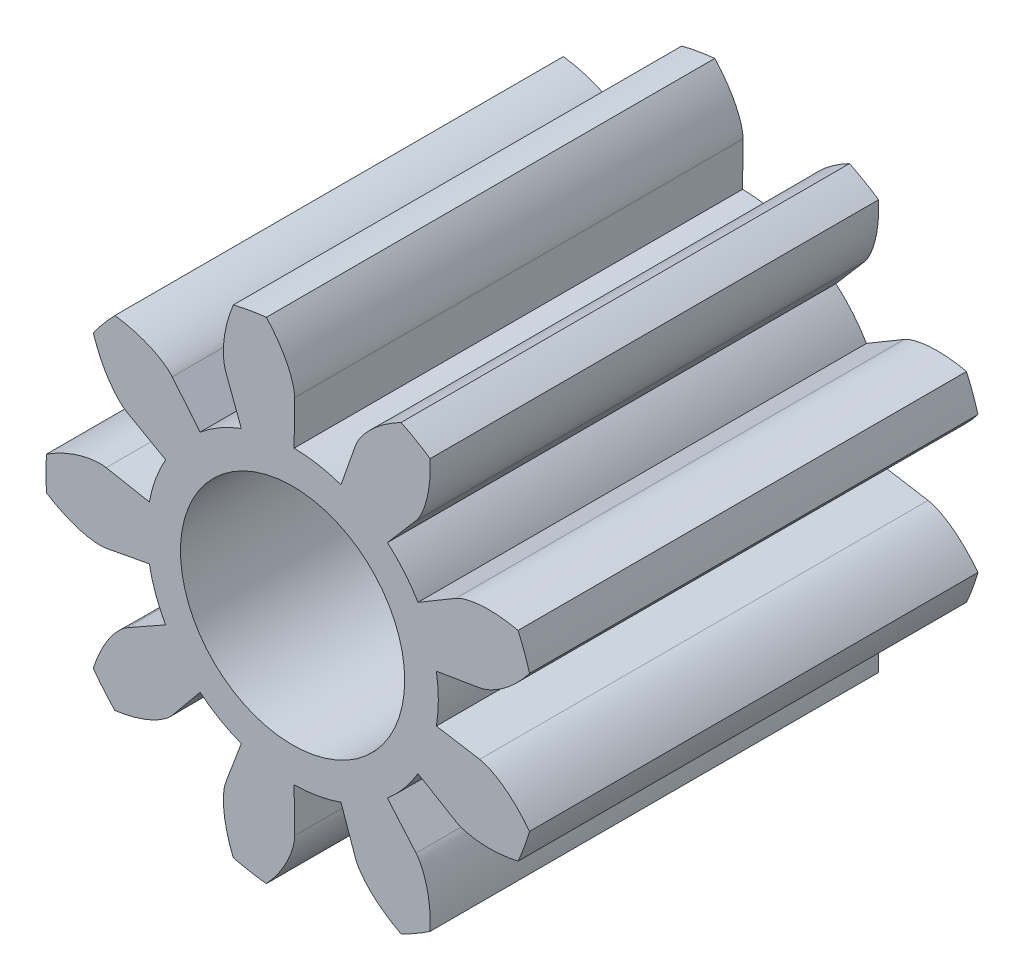
SolidWorks part; units mm, degrees
ref_plane "前视基准面" through (0, 0, 0) normal (0, 0, 1) x (1, 0, 0)
ref_plane "上视基准面" through (0, 0, 0) normal (0, 1, 0) x (1, 0, 0)
ref_plane "右视基准面" through (0, 0, 0) normal (1, 0, 0) x (0, 0, -1)
other "Configuration Table"
sketch "草图1" plane through (0, 0, 0) normal (0, 0, 1) x (1, 0, 0)
  line L0 (0, 0) -> (1.8, 0) construction
  line L1 (0, 0) -> (1.7727, 0.3126) construction
  line L2 (0, 0) -> (1.6688, 0.276)
  line L3 (1.7727, 0.3126) -> (1.7727, -0.3126) construction
  line L4 (0, 0) -> (1.6688, -0.276)
  circle A0 centre (0, 0) radius 2.2
  circle A1 centre (0, 0) radius 1.8 construction
  circle A2 centre (0, 0) radius 1.3
  circle A3 centre (0, 0) radius 1.6914 construction
  circle A4 centre (0, 0) radius 1
  spline S0 degree 4 poles (1.6688, 0.276) (1.6815, 0.2781) (1.7165, 0.2867) (1.7804, 0.3134) (1.8769, 0.3705) (1.9892, 0.4631) (2.115, 0.6012) (2.2366, 0.7836) (2.3401, 1.0009) (2.4181, 1.2482) (2.465, 1.503) (2.4828, 1.7615) (2.473, 2.0332) (2.4258, 2.3665) (2.3192, 2.7541) (2.1304, 3.1816) (1.8506, 3.6185) (1.5097, 4.0103) (1.1213, 4.3527) (0.6893, 4.6421) (0.2307, 4.8777) (-0.2607, 5.0574) (-0.7542, 5.1833) (-1.2841, 5.2523) (-1.6863, 5.2693) (-2.1385, 5.2469) (-2.3948, 5.2166) (-2.6865, 5.1734) (-2.8298, 5.138) (-2.9571, 5.1118) (-2.9949, 5.1006) (-3.0222, 5.094) (-3.037, 5.0905) knots 0 0 0 0 0 0.005604 0.015718 0.02996 0.048734 0.068727 0.096889 0.125051 0.153212 0.181374 0.209535 0.237696 0.271429 0.327752 0.384075 0.440398 0.496721 0.553044 0.609367 0.66569 0.722013 0.778336 0.834659 0.890982 0.909091 0.954545 0.977273 0.988636 0.994318 1 1 1 1 1 construction
  spline S1 degree 4 poles (1.6688, 0.276) (1.6815, 0.2781) (1.7165, 0.2867) (1.7804, 0.3134) (1.8769, 0.3705) (1.9892, 0.4631) (2.115, 0.6012) (2.2366, 0.7836) (2.3401, 1.0009) (2.4181, 1.2482) (2.465, 1.503) (2.4828, 1.7615) (2.473, 2.0332) (2.4258, 2.3665) (2.3192, 2.7541) (2.1304, 3.1816) (1.8506, 3.6185) (1.5097, 4.0103) (1.1213, 4.3527) (0.6893, 4.6421) (0.2307, 4.8777) (-0.2607, 5.0574) (-0.7542, 5.1833) (-1.2841, 5.2523) (-1.6863, 5.2693) (-2.0219, 5.2526) (-2.1774, 5.2392) (-2.215, 5.2356) knots 0 0 0 0 0 0.005604 0.015718 0.02996 0.048734 0.068727 0.096889 0.125051 0.153212 0.181374 0.209535 0.237696 0.271429 0.327752 0.384075 0.440398 0.496721 0.553044 0.609367 0.66569 0.722013 0.778336 0.834659 0.890982 0.909091 0.909091 0.909091 0.909091 0.909091
  spline S2 degree 4 poles (1.6688, -0.276) (1.6815, -0.2781) (1.7165, -0.2867) (1.7804, -0.3134) (1.8769, -0.3705) (1.9892, -0.4631) (2.115, -0.6012) (2.2366, -0.7836) (2.3401, -1.0009) (2.4181, -1.2482) (2.465, -1.503) (2.4828, -1.7615) (2.473, -2.0332) (2.4258, -2.3665) (2.3192, -2.7541) (2.1304, -3.1816) (1.8506, -3.6185) (1.5097, -4.0103) (1.1213, -4.3527) (0.6893, -4.6421) (0.2307, -4.8777) (-0.2607, -5.0574) (-0.7542, -5.1833) (-1.2841, -5.2523) (-1.6863, -5.2693) (-2.1385, -5.2469) (-2.3948, -5.2166) (-2.6865, -5.1734) (-2.8298, -5.138) (-2.9571, -5.1118) (-2.9949, -5.1006) (-3.0222, -5.094) (-3.037, -5.0905) knots 0 0 0 0 0 0.005604 0.015718 0.02996 0.048734 0.068727 0.096889 0.125051 0.153212 0.181374 0.209535 0.237696 0.271429 0.327752 0.384075 0.440398 0.496721 0.553044 0.609367 0.66569 0.722013 0.778336 0.834659 0.890982 0.909091 0.954545 0.977273 0.988636 0.994318 1 1 1 1 1 construction
  spline S3 degree 4 poles (1.6688, -0.276) (1.6815, -0.2781) (1.7165, -0.2867) (1.7804, -0.3134) (1.8769, -0.3705) (1.9892, -0.4631) (2.115, -0.6012) (2.2366, -0.7836) (2.3401, -1.0009) (2.4181, -1.2482) (2.465, -1.503) (2.4828, -1.7615) (2.473, -2.0332) (2.4258, -2.3665) (2.3192, -2.7541) (2.1304, -3.1816) (1.8506, -3.6185) (1.5097, -4.0103) (1.1213, -4.3527) (0.6893, -4.6421) (0.2307, -4.8777) (-0.2607, -5.0574) (-0.7542, -5.1833) (-1.2841, -5.2523) (-1.6863, -5.2693) (-2.0219, -5.2526) (-2.1774, -5.2392) (-2.215, -5.2356) knots 0 0 0 0 0 0.005604 0.015718 0.02996 0.048734 0.068727 0.096889 0.125051 0.153212 0.181374 0.209535 0.237696 0.271429 0.327752 0.384075 0.440398 0.496721 0.553044 0.609367 0.66569 0.722013 0.778336 0.834659 0.890982 0.909091 0.909091 0.909091 0.909091 0.909091
  point P15 (1.7727, 0)
  dimension "齿顶圆直径" = 4.4
  dimension "分度圆直径" = 3.6
  dimension "齿根圆直径" = 2.6
  dimension "基圆直径" = 3.3829
  dimension "内孔直径" = 2
  dimension "渐近线镜像线夹角" = 10
extrude "凸台-拉伸1" add sketch "草图1" along normal blind 4 contours A0 | A4
extrude "切除-拉伸1" cut sketch "草图1<3>" along normal through all contours A2 S3 A0 S1 region at (1.8185, 0, 0)
sketch "草图1<3>" plane through (0, 0, 0) normal (0, 0, 1) x (1, 0, 0) same geometry as "草图1"
pattern_circular "阵列(圆周)1" count 9 every 40 about axis through (0, 0, 4) along (0, 0, 1) of "切除-拉伸1"
equation "\"m\" = 0.4'模数"
equation "\"z\" = 9'齿数"
equation "\"a\"= 20度'压力角"
equation "\"d\"= \"m\" * \"z\"'分度圆直径"
equation "\"da\"= ( \"z\" + 2 ) * \"m\"'齿顶圆直径"
equation "\"df\"= ( \"z\" - 2.5 ) * \"m\"'齿根圆直径"
equation "\"s\"= 0.5 * PI * \"m\"'分度圆齿厚"
equation "\"r\"= 0.38 * \"m\"'齿根圆角"
equation "\"B\"= 0.3 * \"d\"'齿厚"
equation "\"db\"= \"m\" * \"z\" * cos ( \"a\" )'基圆直径"
equation "\"rb\"= \"db\" / 2'基圆半径"
equation "\"齿顶圆直径@草图1\"= \"da\""
equation "\"分度圆直径@草图1\"= \"d\""
equation "\"齿根圆直径@草图1\"= \"df\""
equation "\"基圆直径@草图1\"= \"db\""
equation "\"渐近线镜像线夹角@草图1\"= 360 / 4 / \"z\""
equation "\"h\"= 4'齿轮厚度"
equation "\"ir\" = 2'内孔直径"
equation "\"内孔直径@草图1\"= \"ir\""
equation "\"齿轮厚@凸台-拉伸1\"= \"h\""
equation "\"齿轮夹角@阵列(圆周)1\"= 360 / \"z\""
equation "\"齿数@阵列(圆周)1\"= \"z\""
